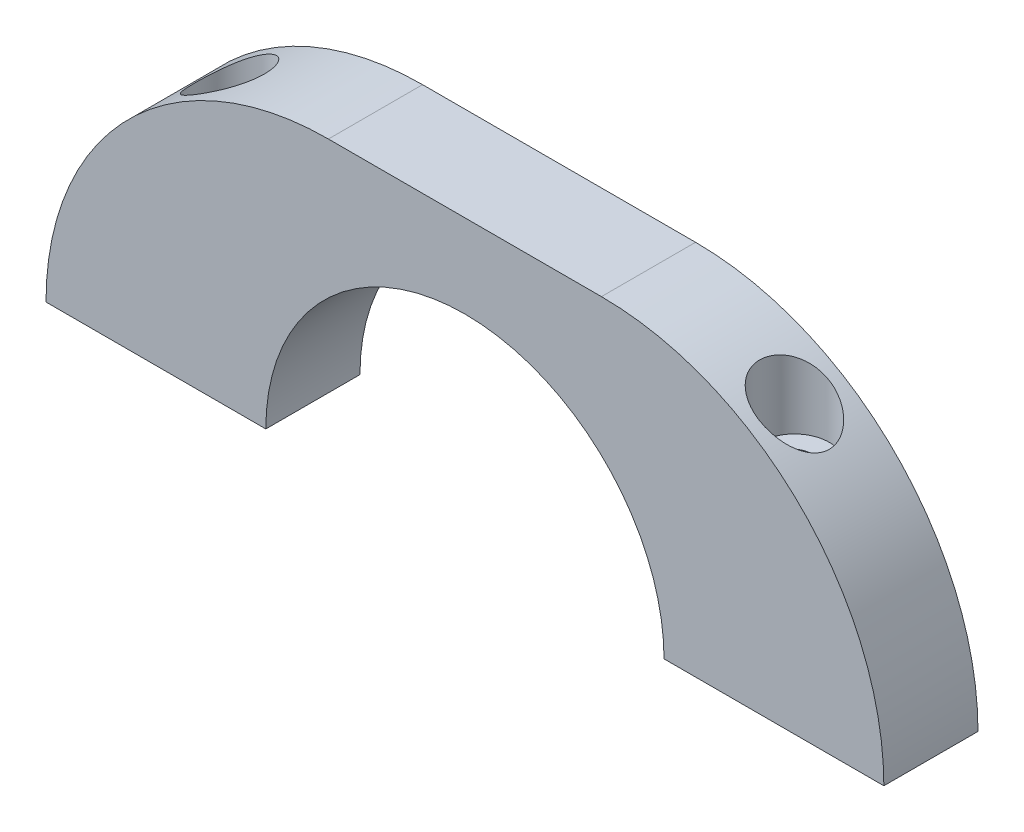
SolidWorks part; units mm, degrees
ref_plane "前视基准面" through (0, 0, 0) normal (0, 0, 1) x (1, 0, 0)
ref_plane "上视基准面" through (0, 0, 0) normal (0, 1, 0) x (1, 0, 0)
ref_plane "右视基准面" through (0, 0, 0) normal (1, 0, 0) x (0, 0, -1)
sketch "草图1" plane through (0, 0, 0) normal (0, 1, 0) x (1, 0, 0)
  line L1 (-44.5, 5) -> (44.5, 5)
  line L2 (-44.5, 5) -> (-44.5, -5)
  line L3 (-44.5, -5) -> (44.5, -5)
  line L4 (44.5, 5) -> (44.5, -5)
  line L5 (-44.5, 5) -> (44.5, -5) construction
  line L6 (-44.5, -5) -> (44.5, 5) construction
  point P0 (0, 0)
  dimension "D1" = 89
  dimension "D2" = 10
extrude "凸台-拉伸1" add sketch "草图1" along normal blind 30
sketch "草图2" plane through (0, 0, 5) normal (0, 0, 1) x (1, 0, 0)
  circle A0 centre (0, 0) radius 21.15
  dimension "D1" = 42.3
extrude "切除-拉伸1" cut sketch "草图2" against normal blind 20
sketch "草图3" plane through (0, 0, 0) normal (0, -1, 0) x (1, 0, 0)
  line L0 (-48.1998, 0) -> (54.4823, 0) construction
  circle A0 centre (-30, 0) radius 1.7
  circle A1 centre (30, 0) radius 1.7
  dimension "D1" = 30
  dimension "D2" = 30
  dimension "D3" = 3.4
  dimension "D4" = 3.4
extrude "切除-拉伸2" cut sketch "草图3" against normal blind 60
sketch "草图4" plane through (0, 30, 0) normal (0, 1, 0) x (1, 0, 0)
  circle A0 centre (-30, 0) radius 3.7
  circle A1 centre (30, 0) radius 3.7
  dimension "D1" = 7.4
  dimension "D2" = 7.4
extrude "切除-拉伸3" cut sketch "草图4" against normal blind 10
fillet "圆角1" radius 30 2 edges at (44.5, 30, 0) (-44.5, 30, 0)
